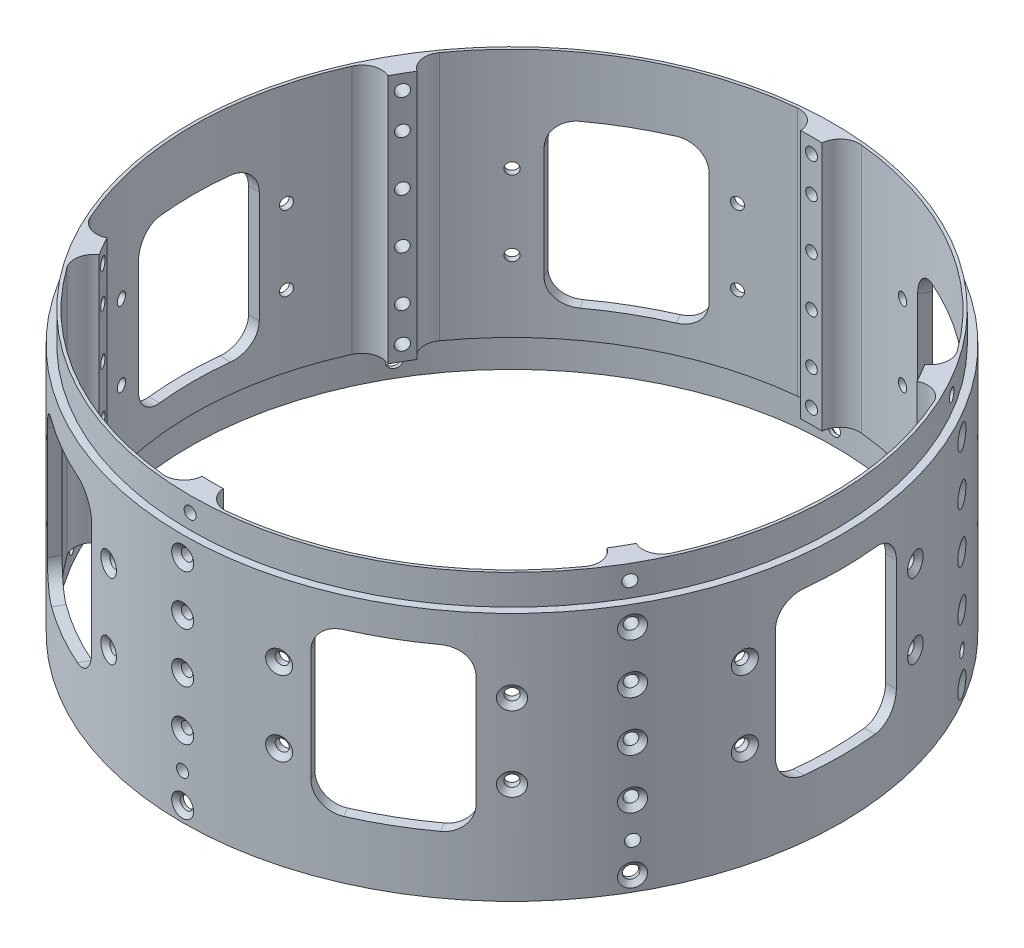
SolidWorks part; units mm, degrees
material "6061-T6 (SS)"
ref_plane "Front Plane" through (0, 0, 0) normal (0, 0, 1) x (1, 0, 0)
ref_plane "Top Plane" through (0, 0, 0) normal (0, 1, 0) x (1, 0, 0)
ref_plane "Right Plane" through (0, 0, 0) normal (1, 0, 0) x (0, 0, -1)
sketch "Sketch1" plane through (0, 0, 0) normal (0, 0, 1) x (1, 0, 0)
  line L0 (0, 42.3951) -> (0, -32.8937) construction
  line L1 (0, -35.6235) -> (0, 35.6235) construction
  line L2 (76.2, -63.5) -> (76.2, 0)
  line L3 (76.2, 0) -> (81.8896, 0)
  line L4 (81.8896, 0) -> (81.8896, -7.6708)
  line L5 (81.8896, -7.6708) -> (83.82, -7.6708)
  line L6 (83.82, -7.6708) -> (83.82, -71.12)
  line L7 (83.82, -71.12) -> (81.9404, -71.12)
  line L8 (81.9404, -71.12) -> (81.9404, -63.5)
  line L9 (81.9404, -63.5) -> (76.2, -63.5)
  line L10 (81.8896, -7.62) -> (84.2911, -7.62) construction
  dimension "D5" = 5.6896
  dimension "D10" = 76.2
  dimension "D2" = 7.62
  dimension "D4" = 7.62
  dimension "D6" = 7.62
revolve "Revolve1" add sketch "Sketch1" angle 360 about L0
sketch "Sketch2" plane through (0, 0, 0) normal (0, 1, 0) x (1, 0, 0)
  line L0 (0, 0) -> (0, 112.6688) construction
  line L1 (0, -35.6235) -> (0, 35.6235) construction
  line L2 (0, 0) -> (-128.6689, 74.287) construction
  line L3 (0, 0) -> (-50.2561, 87.0461) construction
  line L4 (0, 0) -> (-7.6343, 75.8166) construction
  arc A0 (-7.6343, 75.8166) -> (-61.8419, 44.5198) centre (0, 0) ccw construction
  arc A1 (-8.128, 80.7194) -> (-65.841, 47.3988) centre (0, 0) ccw
  arc A2 (-7.1406, 70.9138) -> (-57.8428, 41.6409) centre (0, 0) ccw
  arc A3 (-7.1406, 70.9138) -> (-8.128, 80.7194) centre (-7.6343, 75.8166) ccw
  arc A4 (-65.841, 47.3988) -> (-57.8428, 41.6409) centre (-61.8419, 44.5198) ccw
  circle A5 centre (0, 0) radius 81.8896 construction
  circle A7 centre (0, 0) radius 76.2 construction
  point P5 (-38.1, 65.9911)
  dimension "D2" = 0.762
  dimension "D1" = 60
  dimension "D3" = 30
  dimension "D4" = 5.75
extrude "Cut-Extrude1" cut sketch "Sketch2" against normal through all
pattern_circular "CirPattern1" count 6 over 360 about axis through (0, 42.3951, 0) along (0, 1, 0) of "Cut-Extrude1"
ref_plane "Plane1" through (0, 0, 83.82) normal (0, 0, 1) x (1, 0, 0)
hole_wizard "Tapped Hole for #4-40 Helicoil1" positions "Sketch3" profile "Sketch4" tap size "#4-40" standard "Helicoil® Inch"
sketch "Sketch3" plane through (0, 0, 83.82) normal (0, 0, 1) x (1, 0, 0)
  line L0 (81.8896, 0) -> (-81.8896, 0) construction
  line L1 (2.7181, 0) -> (-2.7181, 0) construction
  line L2 (2.7181, 0) -> (-2.7181, 0) construction
  line L3 (0, 0) -> (0, -3.81) construction
  line L5 (-2.7181, -63.5) -> (2.7181, -63.5) construction
  line L6 (-2.7181, -63.5) -> (2.7181, -63.5) construction
  line L7 (0, -63.5) -> (0, -59.69) construction
  point P0 (0, -3.81)
  point P20 (0, -59.69)
  dimension "D1" = 3.81
  dimension "D2" = 3.81
cosmetic thread "Hole Thread1" parameters "D1"=3.556, "D2"=3.7414
cosmetic thread "Hole Thread6" parameters "D1"=3.556, "D2"=3.7414
sketch "Sketch4" plane through (0, -3.81, 83.82) normal (1, 0, 0) x (0, -1, 0)
  line L0 (0, 0) -> (0, 26.3157)
  line L1 (0, 26.3157) -> (1.524, 25.4)
  line L2 (1.524, 25.4) -> (1.524, 0)
  line L5 (1.524, 0) -> (0, 0)
  line L10 (0, 26.3157) -> (-1.524, 25.4) construction
  line L11 (0, -6.35) -> (0, 107.95) construction
  dimension "Tap Drill Dia." = 3.048
  dimension "Tap Drill Depth" = 25.4
  dimension "Drill Angle" = 118
hole_wizard "CSK for #4 Flat Head Machine Screw (100)1" positions "Sketch5" profile "Sketch6" countersink size "#4" standard "ANSI Inch"
sketch "Sketch5" plane through (0, 0, 83.82) normal (0, 0, 1) x (1, 0, 0)
  line L0 (-2.7181, -63.5) -> (2.7181, -63.5) construction
  line L1 (-2.7181, -63.5) -> (2.7181, -63.5) construction
  line L2 (0, -63.5) -> (0, -67.31) construction
  point P0 (0, -67.31)
  dimension "D1" = 3.81
sketch "Sketch6" plane through (0, -67.31, 83.82) normal (1, 0, 0) x (0, -1, 0)
  line L0 (0, 0) -> (0, 26.3806)
  line L1 (0, 26.3806) -> (1.6319, 25.4)
  line L2 (1.6319, 25.4) -> (1.6319, 1.0284)
  line L3 (1.6319, 1.0284) -> (2.8575, 0)
  line L5 (2.8575, 0) -> (0, 0)
  line L6 (-1.6319, 1.0284) -> (-2.8575, 0) construction
  line L10 (0, 26.3806) -> (-1.632, 25.4) construction
  line L11 (0, -6.35) -> (0, 107.95) construction
  dimension "Hole Dia." = 3.2639
  dimension "Hole Depth" = 25.4
  dimension "Near C'Sink Dia." = 5.715
  dimension "Near C'Sink Angle" = 100
  dimension "Drill Angle" = 118
hole_wizard "CSK for #4 Flat Head Machine Screw (100)3" positions "Sketch12" profile "Sketch13" countersink size "#4" standard "ANSI Inch"
sketch "Sketch12" plane through (0, 0, 83.82) normal (0, 0, 1) x (1, 0, 0)
  line L0 (-2.7181, -63.5) -> (2.7181, -63.5) construction
  line L1 (0, -12.7) -> (0, -38.1) construction
  line L2 (0, -38.1) -> (0, -63.5) construction
  point P0 (0, -38.1)
  point P2 (0, -12.7)
  point P6 (0, -63.5)
  point P7 (0, -25.4)
  point P9 (0, -50.8)
  point P18 (2.6552, -49.599)
  point P19 (3.6591, -26.1918)
  dimension "D1" = 25.4
  dimension "D2" = 50.8
sketch "Sketch13" plane through (0, -38.1, 83.82) normal (1, 0, 0) x (0, -1, 0)
  line L0 (0, 0) -> (0, 26.2852)
  line L1 (0, 26.2852) -> (1.4732, 25.4)
  line L2 (1.4732, 25.4) -> (1.4732, 1.1616)
  line L3 (1.4732, 1.1616) -> (2.8575, 0)
  line L5 (2.8575, 0) -> (0, 0)
  line L6 (-1.4732, 1.1616) -> (-2.8575, 0) construction
  line L10 (0, 26.2852) -> (-1.4732, 25.4) construction
  line L11 (0, -6.35) -> (0, 107.95) construction
  dimension "Hole Dia." = 2.9464
  dimension "Hole Depth" = 25.4
  dimension "Near C'Sink Dia." = 5.715
  dimension "Near C'Sink Angle" = 100
  dimension "Drill Angle" = 118
pattern_circular "CirPattern2" count 6 over 360 about axis through (0, 42.3951, 0) along (0, 1, 0) of "Tapped Hole for #4-40 Helicoil1", "CSK for #4 Flat Head Machine Screw (100)1", "CSK for #4 Flat Head Machine Screw (100)3"
sketch "Sketch7" plane through (0, 0, 0) normal (1, 0, 0) x (0, 0, -1)
  line L1 (-9.017, -15.24) -> (9.017, -15.24)
  line L2 (-15.367, -21.59) -> (-15.367, -50.038)
  line L3 (-9.017, -56.388) -> (9.017, -56.388)
  line L4 (15.367, -21.59) -> (15.367, -50.038)
  line L5 (-15.367, -15.24) -> (15.367, -56.388) construction
  line L6 (-15.367, -56.388) -> (15.367, -15.24) construction
  arc A0 (-15.367, -50.038) -> (-9.017, -56.388) centre (-9.017, -50.038) ccw
  arc A1 (9.017, -56.388) -> (15.367, -50.038) centre (9.017, -50.038) ccw
  arc A2 (15.367, -21.59) -> (9.017, -15.24) centre (9.017, -21.59) ccw
  arc A3 (-9.017, -15.24) -> (-15.367, -21.59) centre (-9.017, -21.59) ccw
  point P0 (0, -35.814)
  dimension "D4" = 6.35
  dimension "D1" = 41.148
  dimension "D2" = 30.734
  dimension "D3" = 15.24
extrude "Cut-Extrude2" cut sketch "Sketch7" against normal through all
sketch "Sketch9" plane through (0, -7.6708, 0) normal (0, 1, 0) x (1, 0, 0)
  line L0 (-49.5, 0) -> (-83.82, 0)
  line L1 (-50.2347, -13.4603) -> (-80.9639, -21.6942)
  line L2 (-83.82, 11.0351) -> (-83.82, -11.0351) construction
  line L3 (-83.82, -11.0351) -> (-78.1078, -32.3533) construction
  arc A0 (-83.3336, 9.017) -> (-83.3336, -9.017) centre (0, 0) ccw construction
  circle A1 centre (0, 0) radius 83.82 construction
  dimension "D1" = 15
ref_plane "Plane3" through (-80.9639, -7.6708, 21.6942) normal (-0.9659, 0, 0.2588) x (0.2588, 0, 0.9659)
hole_wizard "CSK for #4 Flat Head Machine Screw (100)2" positions "Sketch10" profile "Sketch11" countersink size "#4" standard "ANSI Inch"
sketch "Sketch10" plane through (-80.9639, -7.6708, 21.6942) normal (-0.9659, 0, 0.2588) x (0.2588, 0, 0.9659)
  line L0 (0, 0) -> (0, -18.6182) construction
  line L1 (0, -18.6182) -> (0, -37.6682) construction
  line L5 (0, -28.1432) -> (-6.4831, -28.1432) construction
  line L8 (-6.4831, -13.9192) -> (-6.4831, -42.3672) construction
  point P0 (0, -18.6182)
  point P2 (0, -37.6682)
  dimension "D1" = 19.05
sketch "Sketch11" plane through (-80.9639, -26.289, 21.6942) normal (0, 1, 0) x (0.2588, 0, 0.9659)
  line L0 (0, 0) -> (0, 26.2852)
  line L1 (0, 26.2852) -> (1.4732, 25.4)
  line L2 (1.4732, 25.4) -> (1.4732, 1.1616)
  line L3 (1.4732, 1.1616) -> (2.8575, 0)
  line L5 (2.8575, 0) -> (0, 0)
  line L6 (-1.4732, 1.1616) -> (-2.8575, 0) construction
  line L10 (0, 26.2852) -> (-1.4732, 25.4) construction
  line L11 (0, -6.35) -> (0, 107.95) construction
  dimension "Hole Dia." = 2.9464
  dimension "Hole Depth" = 25.4
  dimension "Near C'Sink Dia." = 5.715
  dimension "Near C'Sink Angle" = 100
  dimension "Drill Angle" = 118
mirror "Mirror1" about plane through (0, 0, 0) normal (0, 0, 1) of "CSK for #4 Flat Head Machine Screw (100)2"
pattern_circular "CirPattern5" count 6 over 360 about axis through (0, -7.6708, 0) along (0, 1, 0) of "Cut-Extrude2", "Mirror1"
ref_plane "Plane2" [suppressed] through (0, 0, 0) normal (-0.7071, 0, 0.7071) x (0.7071, 0, 0.7071)
sketch "Sketch8" [suppressed] plane through (0, 0, 0) normal (-0.7071, 0, 0.7071) x (0.7071, 0, 0.7071)
  line L0 (0, 0) -> (89.1919, 0) construction
  line L1 (-9.017, -17.145) -> (-6.858, -17.145)
  line L2 (-12.192, -20.32) -> (-12.192, -31.115)
  line L3 (-9.017, -34.29) -> (-6.858, -34.29)
  line L4 (-3.683, -20.32) -> (-3.683, -31.115)
  line L5 (0, 0) -> (0, -89.2767) construction
  line L6 (-83.82, -71.12) -> (83.82, -71.12) construction
  line L7 (-7.9375, -52.07) -> (-4.7625, -52.07)
  line L8 (-9.525, -53.6575) -> (-9.525, -56.8325)
  line L9 (-7.9375, -58.42) -> (-4.7625, -58.42)
  line L10 (-3.175, -53.6575) -> (-3.175, -56.8325)
  arc A0 (-9.017, -34.29) -> (-12.192, -31.115) centre (-9.017, -31.115) cw
  arc A1 (-3.683, -31.115) -> (-6.858, -34.29) centre (-6.858, -31.115) cw
  arc A2 (-3.683, -20.32) -> (-6.858, -17.145) centre (-6.858, -20.32) ccw
  arc A3 (-9.017, -17.145) -> (-12.192, -20.32) centre (-9.017, -20.32) ccw
  arc A4 (-9.525, -56.8325) -> (-7.9375, -58.42) centre (-7.9375, -56.8325) ccw
  arc A5 (-3.175, -56.8325) -> (-4.7625, -58.42) centre (-4.7625, -56.8325) cw
  arc A6 (-3.175, -53.6575) -> (-4.7625, -52.07) centre (-4.7625, -53.6575) ccw
  arc A7 (-7.9375, -52.07) -> (-9.525, -53.6575) centre (-7.9375, -53.6575) ccw
  circle A8 centre (-6.35, -48.895) radius 1.5875
  circle A9 centre (-6.35, -61.595) radius 1.5875
  point P20 (-3.175, -55.245)
  point P29 (-6.35, -58.42)
  dimension "D1" = 3.175
  dimension "D8" = 1.5875
  dimension "D11" = 3.175
  dimension "D12" = 3.175
  dimension "D2" = 8.509
  dimension "D3" = 17.145
  dimension "D4" = 17.145
  dimension "D5" = 3.683
  dimension "D6" = 6.35
  dimension "D7" = 6.35
  dimension "D9" = 6.35
  dimension "D10" = 12.7
  dimension "D13" = 3.175
  dimension "D14" = 3.175
extrude "Cut-Extrude3" [suppressed] cut sketch "Sketch8" along normal through all
equation "\"nominalLength\"=2.5"
equation "\"D8@Sketch1\"=\"nominalLength\""
equation "\"D12@Sketch8\"=\"D11@Sketch8\""
